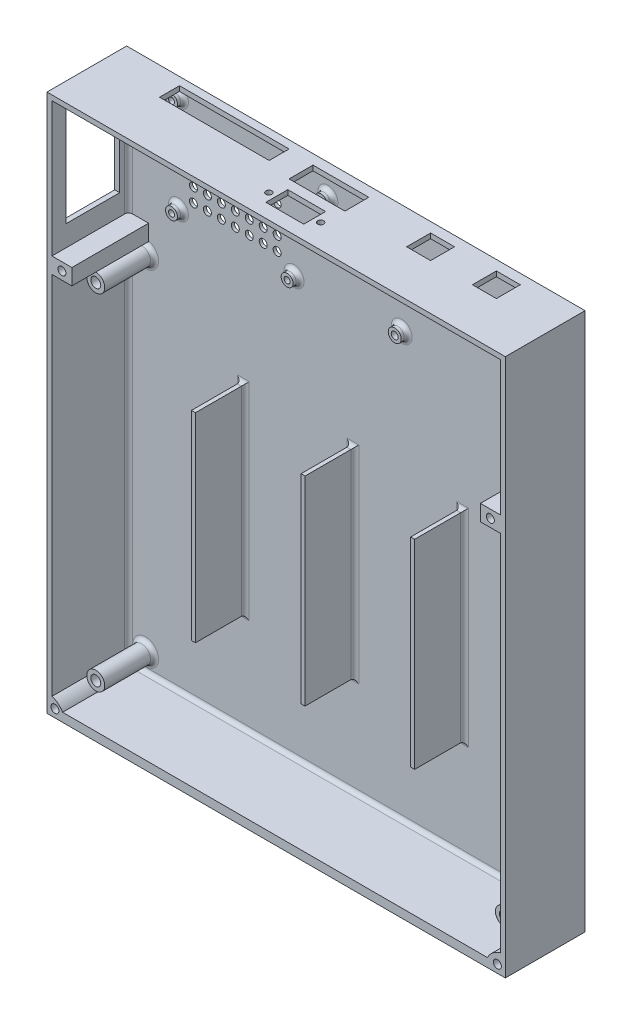
SolidWorks part; units mm, degrees
ref_plane "Plan de face" through (0, 0, 0) normal (0, 0, 1) x (1, 0, 0)
ref_plane "Plan de dessus" through (0, 0, 0) normal (0, 1, 0) x (1, 0, 0)
ref_plane "Plan de droite" through (0, 0, 0) normal (1, 0, 0) x (0, 0, -1)
sketch "Esquisse1" plane through (0, 0, 0) normal (0, 0, 1) x (1, 0, 0)
  line L0 (0, 136.5625) -> (0, -142.8125) construction
  line L1 (-195, -41.5625) -> (201.25, -41.5625) construction
  line L2 (115, 93.4375) -> (-115, 93.4375)
  line L3 (-115, 93.4375) -> (-115, -176.5625)
  line L4 (115, -176.5625) -> (-115, -176.5625)
  line L6 (115, 93.4375) -> (115, -176.5625)
  point P10 (-115, -41.5625)
  point P12 (0, 93.4375)
  dimension "D1" = 115
  dimension "D2" = 135
extrude "Boss.-Extru.1" add sketch "Esquisse1" along normal blind 5
sketch "Esquisse2" plane through (0, 0, 5) normal (0, 0, 1) x (1, 0, 0)
  line L0 (-115, -176.5625) -> (115, -176.5625) construction
  line L1 (-115, 93.4375) -> (-115, -176.5625) construction
  line L2 (-1.5, 152.9836) -> (-1.5, -221.0762) construction
  line L3 (-154.951, -77.0625) -> (207.3243, -77.0625) construction
  line L4 (115, 93.4375) -> (-115, 93.4375) construction
  line L5 (115, -176.5625) -> (115, 93.4375) construction
  line L6 (152.1134, 61.4375) -> (-165.3137, 61.4375) construction
  line L7 (-58.5, 134.3556) -> (-58.5, 23.9251) construction
  line L8 (-25.2083, 61.4375) -> (-76.5448, 61.4375) construction
  line L9 (-2, 113.0864) -> (-2, 66.437) construction
  line L10 (-19.2346, 73.6875) -> (13.2189, 73.6875) construction
  circle A0 centre (-104, -163.5625) radius 2
  circle A7 centre (-104, 9.4375) radius 2
  circle A8 centre (104.5, 82.9375) radius 1.75
  circle A9 centre (24.5, 82.9375) radius 1.75
  circle A10 centre (24.5, 39.9375) radius 1.75
  circle A11 centre (104.5, 39.9375) radius 1.75
  circle A12 centre (-87.5, 85.9375) radius 1.5
  circle A13 centre (-29.5, 85.9375) radius 1.5
  circle A116 centre (8.5, 67.4375) radius 1.5
  circle A117 centre (-12.5, 67.4375) radius 1.5
  circle A118 centre (-12.5, 79.9375) radius 1.5
  circle A119 centre (8.5, 79.9375) radius 1.5
  circle A120 centre (101, -163.5625) radius 2
  circle A121 centre (101, 9.4375) radius 2
  circle A122 centre (-87.5, 36.9375) radius 1.5
  circle A123 centre (-29.5, 36.9375) radius 1.5
  dimension "D1" = 4
  dimension "D4" = 26
  dimension "D10" = 3.5
  dimension "D11" = 3.5
  dimension "D13" = 3
  dimension "D17" = 24.5
  dimension "D21" = 10.5
  dimension "D22" = 3
  dimension "D20" = 102.5
  dimension "D2" = 13
  dimension "D3" = 11
  dimension "D5" = 86.5
  dimension "D6" = 10.5
  dimension "D7" = 10.5
  dimension "D8" = 10.5
  dimension "D9" = 80
  dimension "D12" = 21.5
  dimension "D14" = 27.5
  dimension "D15" = 7.5
  dimension "D16" = 29
  dimension "D23" = 6.25
extrude "Enlèv. mat.-Extru.1" cut sketch "Esquisse2" against normal blind 5
shell "Coque3" thickness 1.5 removed face at (102.75, 39.9375, 5)
sketch "Esquisse3" plane through (0, 0, 1.5) normal (0, 0, 1) x (1, 0, 0)
  line L0 (-1.5, 104.4372) -> (-1.5, -196.0583) construction
  line L1 (104, -77.0625) -> (-172.0752, -77.0625) construction
  circle A0 centre (-104, 9.4375) radius 4.5
  circle A4 centre (-104, -163.5625) radius 4.5
  circle A5 centre (-104, 9.4375) radius 2.5
  circle A6 centre (-104, -163.5625) radius 2.5
  circle A8 centre (101, -163.5625) radius 4.5
  circle A9 centre (101, -163.5625) radius 2.5
  circle A10 centre (101, 9.4375) radius 4.5
  circle A11 centre (101, 9.4375) radius 2.5
  dimension "D1" = 9
  dimension "D2" = 5
  dimension "D4" = 102.5
  dimension "D3" = 86.5
extrude "Boss.-Extru.3" add sketch "Esquisse3" along normal blind 25
sketch "Esquisse4" plane through (0, 0, 1.5) normal (0, 0, 1) x (1, 0, 0)
  line L0 (-113.5, -175.0625) -> (113.5, -175.0625) construction
  line L1 (-113.5, 91.9375) -> (-112.5, 91.9375)
  line L2 (-113.5, 91.9375) -> (-113.5, -175.0625)
  line L3 (-113.5, -175.0625) -> (-112.5, -175.0625)
  line L4 (-112.5, 91.9375) -> (-112.5, -175.0625)
  line L5 (0, 95.4885) -> (0, -188.2553) construction
  line L6 (113.5, -175.0625) -> (112.5, -175.0625)
  line L7 (113.5, 91.9375) -> (113.5, -175.0625)
  line L8 (113.5, 91.9375) -> (112.5, 91.9375)
  line L9 (112.5, 91.9375) -> (112.5, -175.0625)
  dimension "D1" = 1
extrude "Boss.-Extru.4" add sketch "Esquisse4" along normal blind 3.5
sketch "Esquisse5" plane through (0, 0, 1.5) normal (0, 0, 1) x (1, 0, 0)
  line L0 (112.5, 91.9375) -> (112.5, -175.0625) construction
  line L1 (-112.5, 91.9375) -> (112.5, 91.9375)
  line L2 (-112.5, 91.9375) -> (-112.5, 90.9375)
  line L3 (-112.5, 90.9375) -> (112.5, 90.9375)
  line L4 (112.5, 91.9375) -> (112.5, 90.9375)
  line L5 (-112.5, -175.0625) -> (-112.5, 91.9375) construction
  line L6 (-196.2712, -42.5625) -> (155.2477, -42.5625) construction
  line L7 (-112.5, -172.1625) -> (112.5, -172.1625)
  line L8 (-112.5, -172.1625) -> (-112.5, -175.0625)
  line L9 (-112.5, -175.0625) -> (112.5, -175.0625)
  line L10 (112.5, -172.1625) -> (112.5, -175.0625)
  dimension "D1" = 1
  dimension "D2" = 133.5
  dimension "D3" = 2.9
extrude "Boss.-Extru.10" add sketch "Esquisse5" along normal blind 3.5
sketch "Esquisse7" plane through (0, 0, 1.5) normal (0, 0, 1) x (1, 0, 0)
  line L0 (1, -22.1625) -> (1, -122.1625)
  line L5 (-1, -22.1625) -> (1, -22.1625)
  line L6 (-151.213, -61.5625) -> (245.9243, -61.5625) construction
  line L57 (-1, -22.1625) -> (-1, -122.1625)
  line L58 (-56, -22.1625) -> (-54, -22.1625)
  line L59 (-56, -22.1625) -> (-56, -122.1625)
  line L60 (-56, -122.1625) -> (-54, -122.1625)
  line L61 (-54, -22.1625) -> (-54, -122.1625)
  line L62 (-1, -122.1625) -> (1, -122.1625)
  line L63 (56, -22.1625) -> (56, -122.1625)
  line L64 (54, -22.1625) -> (56, -22.1625)
  line L65 (54, -22.1625) -> (54, -122.1625)
  line L66 (54, -122.1625) -> (56, -122.1625)
  line L67 (-112.5, -172.1625) -> (-112.5, 90.9375) construction
  line L68 (112.5, -172.1625) -> (-112.5, -172.1625) construction
  dimension "D1" = 2
  dimension "D2" = 100
  dimension "D3" = 3
  dimension "D4" = 56.5
  dimension "D5" = 50
extrude "Boss.-Extru.11" add sketch "Esquisse7" along normal blind 25
sketch "Esquisse8" plane through (0, 0, 5) normal (0, 0, 1) x (1, 0, 0)
  line L0 (-112.5, 90.9375) -> (-112.5, -172.1625)
  line L1 (-112.5, -172.1625) -> (112.5, -172.1625)
  line L2 (112.5, -172.1625) -> (112.5, 90.9375)
  line L3 (112.5, 90.9375) -> (-112.5, 90.9375)
  line L4 (-115, 93.4375) -> (-115, -176.5625)
  line L5 (-115, -176.5625) -> (115, -176.5625)
  line L6 (115, -176.5625) -> (115, 93.4375)
  line L7 (115, 93.4375) -> (-115, 93.4375)
extrude "Boss.-Extru.12" add sketch "Esquisse8" along normal blind 35
fillet "Congé1" radius 2 32 edges at (-54, -72.1625, 1.5) (-55, -22.1625, 1.5) (-56, -72.1625, 1.5) (-108.5, -163.5625, 1.5) (96.5, -163.5625, 1.5) (-108.5, 9.4375, 1.5) (-90.5, 85.9375, 1.5) (-32.5, 85.9375, 1.5) (5.5, 67.4375, 1.5) (101.25, 82.9375, 1.5) (21.25, 82.9375, 1.5) (21.25, 39.9375, 1.5) (101.25, 39.9375, 1.5) (5.5, 79.9375, 1.5) (-15.5, 79.9375, 1.5) (-15.5, 67.4375, 1.5) (-112.5, -40.6125, 1.5) (0, 90.9375, 1.5) (112.5, -40.6125, 1.5) (0, -172.1625, 1.5) (96.5, 9.4375, 1.5) (-90.5, 36.9375, 1.5) (-32.5, 36.9375, 1.5) (55, -122.1625, 1.5) (56, -72.1625, 1.5) (55, -22.1625, 1.5) (54, -72.1625, 1.5) (-55, -122.1625, 1.5) (0, -122.1625, 1.5) (1, -72.1625, 1.5) (0, -22.1625, 1.5) (-1, -72.1625, 1.5)
sketch "Esquisse11" plane through (0, 90.9375, 0) normal (0, -1, 0) x (1, 0, 0)
  line L0 (-112.5, 3.5) -> (112.5, 3.5) construction
  line L1 (-84.5, 14) -> (-29.5, 14)
  line L2 (-84.5, 14) -> (-84.5, 4)
  line L3 (-84.5, 4) -> (-29.5, 4)
  line L4 (-29.5, 14) -> (-29.5, 4)
  line L5 (-112.5, 40) -> (-112.5, 3.5) construction
  line L6 (112.5, 40) -> (-112.5, 40) construction
  line L7 (-16.5, 17) -> (11.5, 17)
  line L8 (-16.5, 17) -> (-16.5, 5)
  line L9 (-16.5, 5) -> (11.5, 5)
  line L10 (11.5, 17) -> (11.5, 5)
  line L11 (42.5, 17) -> (54.5, 17)
  line L12 (42.5, 17) -> (42.5, 5)
  line L13 (42.5, 5) -> (54.5, 5)
  line L14 (54.5, 17) -> (54.5, 5)
  line L16 (115, 0) -> (-115, 0) construction
  line L17 (76.86, 6.6) -> (86.86, 6.6) construction
  line L18 (75.5, 17) -> (87.5, 17)
  line L19 (75.5, 17) -> (75.5, 5)
  line L20 (75.5, 5) -> (87.5, 5)
  line L21 (87.5, 17) -> (87.5, 5)
  dimension "D2" = 10
  dimension "D3" = 55
  dimension "D4" = 28
  dimension "D5" = 12
  dimension "D6" = 28
  dimension "D7" = 13
  dimension "D8" = 12
  dimension "D9" = 31
  dimension "D10" = 23
  dimension "D11" = 1.5
  dimension "D12" = 4
  dimension "D13" = 21
  dimension "D14" = 12
  dimension "D15" = 23
  dimension "D16" = 1.6
extrude "Enlèv. mat.-Extru.3" cut sketch "Esquisse11" against normal blind 10
sketch "Esquisse13" plane through (-112.5, 0, 0) normal (1, 0, 0) x (0, 0, -1)
  line L2 (-33, 88.9375) -> (-33, 33.9375)
  line L6 (-40, 93.4375) -> (-40, -176.5625) construction
  line L8 (-33, 88.9375) -> (-6, 88.9375)
  line L9 (-6, 88.9375) -> (-6, 33.9375)
  line L10 (-6, 33.9375) -> (-33, 33.9375)
  line L11 (-40, 93.4375) -> (0, 93.4375) construction
  line L12 (0, 93.4375) -> (0, -176.5625) construction
  dimension "D1" = 4.5
  dimension "D2" = 55
  dimension "D3" = 7
  dimension "D4" = 6
extrude "Enlèv. mat.-Extru.4" cut sketch "Esquisse13" against normal blind 10
sketch "Esquisse14" plane through (0, 0, 1.5) normal (0, 0, 1) x (1, 0, 0)
  line L0 (-33.5, 88.9375) -> (-83.5, 88.9375) construction
  line L1 (-110.5, 88.9375) -> (-110.5, 9.4375) construction
  circle A0 centre (-80, 78.4375) radius 2
  circle A1 centre (-73, 78.4375) radius 2
  circle A2 centre (-66, 78.4375) radius 2
  circle A3 centre (-59, 78.4375) radius 2
  circle A4 centre (-52, 78.4375) radius 2
  circle A5 centre (-45, 78.4375) radius 2
  circle A6 centre (-38, 78.4375) radius 2
  circle A7 centre (-73, 71.4375) radius 2
  circle A8 centre (-66, 71.4375) radius 2
  circle A9 centre (-59, 71.4375) radius 2
  circle A10 centre (-52, 71.4375) radius 2
  circle A11 centre (-45, 71.4375) radius 2
  circle A12 centre (-38, 71.4375) radius 2
  circle A13 centre (-73, 64.4375) radius 2
  circle A14 centre (-66, 64.4375) radius 2
  circle A15 centre (-59, 64.4375) radius 2
  circle A16 centre (-52, 64.4375) radius 2
  circle A17 centre (-45, 64.4375) radius 2
  circle A18 centre (-38, 64.4375) radius 2
  circle A19 centre (-73, 57.4375) radius 2
  circle A20 centre (-66, 57.4375) radius 2
  circle A21 centre (-59, 57.4375) radius 2
  circle A22 centre (-52, 57.4375) radius 2
  circle A23 centre (-45, 57.4375) radius 2
  circle A24 centre (-38, 57.4375) radius 2
  circle A25 centre (-73, 50.4375) radius 2
  circle A26 centre (-66, 50.4375) radius 2
  circle A27 centre (-59, 50.4375) radius 2
  circle A28 centre (-52, 50.4375) radius 2
  circle A29 centre (-45, 50.4375) radius 2
  circle A30 centre (-38, 50.4375) radius 2
  circle A31 centre (-73, 43.4375) radius 2
  circle A32 centre (-66, 43.4375) radius 2
  circle A33 centre (-59, 43.4375) radius 2
  circle A34 centre (-52, 43.4375) radius 2
  circle A35 centre (-45, 43.4375) radius 2
  circle A36 centre (-38, 43.4375) radius 2
  circle A37 centre (-80, 71.4375) radius 2
  circle A38 centre (-80, 64.4375) radius 2
  circle A39 centre (-80, 57.4375) radius 2
  circle A40 centre (-80, 50.4375) radius 2
  circle A41 centre (-80, 43.4375) radius 2
  dimension "D1" = 4
  dimension "D2" = 10.5
  dimension "D3" = 30.5
  dimension "D4" = 7
  dimension "D5" = 6
extrude "Enlèv. mat.-Extru.5" cut sketch "Esquisse14" against normal blind 10
sketch "Esquisse15" plane through (0, 0, 0) normal (0, 0, -1) x (-1, 0, 0)
  line L0 (115, -176.5625) -> (-115, -176.5625) construction
  line L1 (115, -176.5625) -> (106, -176.5625)
  line L2 (115, -176.5625) -> (115, -167.5625)
  line L5 (115, 93.4375) -> (115, -176.5625) construction
  arc A0 (115, -167.5625) -> (106, -176.5625) centre (115, -176.5625) ccw
  dimension "D1" = 0
  dimension "D2" = 0
extrude "Boss.-Extru.13" add sketch "Esquisse15" against normal up to surface (40 mm away) up to face at (0, -41.5625, 40)
sketch "Esquisse16" plane through (0, 0, 26.5) normal (0, 0, 1) x (1, 0, 0)
  line L0 (115, -176.5625) -> (115, 93.4375) construction
  line L3 (105, -176.5625) -> (115, -176.5625)
  line L4 (115, -166.5625) -> (115, -176.5625)
  line L5 (-115, -176.5625) -> (115, -176.5625) construction
  arc A1 (105, -176.5625) -> (115, -166.5625) centre (115, -176.5625) cw
  dimension "D1" = 0
  dimension "D2" = 0
extrude "Boss.-Extru.14" add sketch "Esquisse16" against normal up to surface (26.5 mm away) from surface up to face at (0, -41.5625, 0) starting at face at (-21.3461, -65.9679, 40)
sketch "Esquisse17" plane through (0, 0, 26.5) normal (0, 0, 1) x (1, 0, 0)
  line L0 (-115, -176.5625) -> (115, -176.5625) construction
  line L2 (-115, 93.4375) -> (-115, -176.5625) construction
  circle A0 centre (-111, -172.5625) radius 2
  dimension "D1" = 4
  dimension "D2" = 4
extrude "Enlèv. mat.-Extru.6" cut sketch "Esquisse17" against normal up to surface (26.5 mm away) from surface up to face at (0, -41.5625, 0) starting at face at (-0.2148, -82.6683, 40)
sketch "Esquisse18" plane through (0, 0, 26.5) normal (0, 0, 1) x (1, 0, 0)
  line L0 (-115, -176.5625) -> (115, -176.5625) construction
  line L1 (115, -176.5625) -> (115, 93.4375) construction
  circle A0 centre (111, -172.5625) radius 2
  dimension "D1" = 4
  dimension "D2" = 4
extrude "Enlèv. mat.-Extru.7" cut sketch "Esquisse18" against normal up to surface (26.5 mm away) from surface up to face at (-113, -172.5625, 0) starting at face at (-109, -172.5625, 40)
sketch "Esquisse21" plane through (0, 93.4375, 0) normal (0, 1, 0) x (1, 0, 0)
  line L0 (115, -40) -> (-115, -40) construction
  line L1 (-12.1571, -22) -> (6.8429, -22)
  line L2 (-12.1571, -22) -> (-12.1571, -33)
  line L3 (-12.1571, -33) -> (6.8429, -33)
  line L4 (6.8429, -22) -> (6.8429, -33)
  circle A0 centre (10.3429, -28) radius 1.5
  circle A1 centre (-15.6571, -28) radius 1.5
  point P8 (6.8429, -27.5)
  dimension "D2" = 3.5
  dimension "D3" = 26
  dimension "D4" = 5
  dimension "D1" = 7
  dimension "D5" = 5
  dimension "D6" = 19
extrude "Enlèv. mat.-Extru.8" cut sketch "Esquisse21" against normal up to surface (2.5 mm away) up to face at (-57, 90.9375, 9)
sketch "Esquisse28" plane through (0, 0, 1.5) normal (0, 0, 1) x (1, 0, 0)
  line L0 (112.5, 90.9375) -> (112.5, -166.88) construction
  line L1 (102.5, 23.4375) -> (112.5, 23.4375)
  line L2 (102.5, 23.4375) -> (102.5, 15.4375)
  line L3 (102.5, 15.4375) -> (112.5, 15.4375)
  line L4 (112.5, 23.4375) -> (112.5, 15.4375)
  circle A0 centre (101, 9.4375) radius 2.5 construction
  point P6 (112.5, 19.4375)
  dimension "D4" = 6
  dimension "D1" = 8
  dimension "D2" = 10
  dimension "D3" = 0
extrude "Boss.-Extru.16" add sketch "Esquisse28" along normal up to surface (38.5 mm away) up to face at (113, -172.5625, 40)
sketch "Esquisse29" plane through (0, 0, 40) normal (0, 0, 1) x (1, 0, 0)
  line L0 (112.5, 23.4375) -> (102.5, 23.4375) construction
  line L1 (102.5, 23.4375) -> (102.5, 15.4375) construction
  circle A0 centre (107.5, 19.4375) radius 2
  dimension "D1" = 4
  dimension "D2" = 5
extrude "Enlèv. mat.-Extru.10" cut sketch "Esquisse29" against normal through all
sketch "Esquisse30" plane through (0, 0, 1.5) normal (0, 0, 1) x (1, 0, 0)
  line L0 (-112.5, 90.9375) -> (-112.5, -167.9167) construction
  line L1 (-112.5, 23.4375) -> (-102.5, 23.4375)
  line L2 (-112.5, 23.4375) -> (-112.5, 15.4375)
  line L3 (-112.5, 15.4375) -> (-102.5, 15.4375)
  line L4 (-102.5, 23.4375) -> (-102.5, 15.4375)
  circle A0 centre (-104, 9.4375) radius 2.5 construction
  dimension "D1" = 10
  dimension "D2" = 8
  dimension "D3" = 6
  dimension "D4" = 0
extrude "Boss.-Extru.17" add sketch "Esquisse30" along normal up to surface (38.5 mm away) up to face at (109.5, 19.4375, 40)
sketch "Esquisse31" plane through (0, 0, 40) normal (0, 0, 1) x (1, 0, 0)
  line L0 (-102.5, 23.4375) -> (-112.5, 23.4375) construction
  line L1 (-102.5, 15.4375) -> (-102.5, 23.4375) construction
  circle A0 centre (-107.5, 19.4375) radius 2
  dimension "D1" = 4
  dimension "D2" = 5
extrude "Enlèv. mat.-Extru.11" cut sketch "Esquisse31" against normal through all
